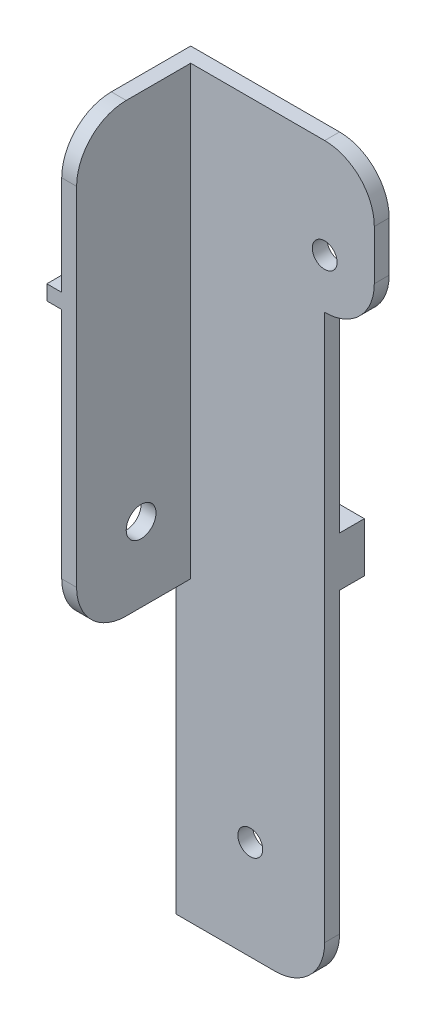
SolidWorks part; units mm, degrees
ref_plane "Front Plane" through (0, 0, 0) normal (0, 0, 1) x (1, 0, 0)
ref_plane "Top Plane" through (0, 0, 0) normal (0, 1, 0) x (1, 0, 0)
ref_plane "Right Plane" through (0, 0, 0) normal (1, 0, 0) x (0, 0, -1)
sketch "Sketch1" plane through (0, 0, 0) normal (0, 0, 1) x (1, 0, 0)
  line L0 (15, 0) -> (15, 150) construction
  line L1 (0, 0) -> (30, 0)
  line L2 (0, 0) -> (0, 150)
  line L3 (0, 150) -> (30, 150)
  line L4 (30, 0) -> (30, 120)
  line L5 (30, 150) -> (40, 150)
  line L7 (30, 120) -> (40, 120)
  line L8 (40, 150) -> (40, 120)
  line L9 (15, 75) -> (30, 75) construction
  line L10 (15, 75) -> (0, 75) construction
  line L12 (30, 75) -> (0, 75)
  line L13 (30, 75) -> (30, 80)
  line L14 (30, 80) -> (0, 80)
  line L15 (0, 75) -> (0, 80)
  line L16 (0, 75) -> (30, 75)
  line L17 (0, 75) -> (0, 70)
  line L18 (0, 70) -> (30, 70)
  line L19 (30, 75) -> (30, 70)
  circle A0 centre (15, 20) radius 2.5
  circle A1 centre (30, 130) radius 2.5
  dimension "D7" = 5
  dimension "D8" = 5
  dimension "D1" = 150
  dimension "D2" = 30
  dimension "D3" = 30
  dimension "D4" = 10
  dimension "D5" = 5
  dimension "D6" = 20
  dimension "D9" = 5
extrude "Boss-Extrude1" add sketch "Sketch1" along normal blind 3 contours L14 L4 L7 L8 L5 L3 L2 A1 | L18 L2 L1 L4 A0 region at (15, 35.1416, 0) region at (17.3969, 117.3969, 0)
sketch "Sketch2" plane through (0, 0, 3) normal (0, 0, 1) x (1, 0, 0)
  line L1 (30, 70) -> (0, 70)
  line L2 (30, 70) -> (30, 80)
  line L3 (30, 80) -> (0, 80)
  line L4 (0, 70) -> (0, 80)
extrude "Boss-Extrude2" add sketch "Sketch2" against normal blind 8
sketch "Sketch3" plane through (0, 0, 3) normal (0, 0, 1) x (1, 0, 0)
  line L0 (0, 0) -> (30, 0) construction
  line L1 (0, 150) -> (3, 150)
  line L2 (0, 150) -> (0, 0)
  line L3 (0, 0) -> (3, 0)
  line L4 (3, 150) -> (3, 0)
  dimension "D1" = 3
extrude "Boss-Extrude3" add sketch "Sketch3" along normal blind 23
sketch "Sketch4" plane through (0, 0, 0) normal (-1, 0, 0) x (0, 0, 1)
  line L0 (13, 150) -> (13, 0)
  line L1 (26, 150) -> (0, 150) construction
  line L2 (26, 0) -> (0, 0) construction
  circle A0 centre (13, 75) radius 3
  dimension "D1" = 6
extrude "Cut-Extrude1" cut sketch "Sketch4" against normal blind 23 contours L0 A0 | L0 A0 region at (0, 75, 14.2732) region at (0, 75, 11.7268)
sketch "Sketch5" plane through (0, 0, 0) normal (-1, 0, 0) x (0, 0, 1)
  line L0 (26, 150) -> (26, 0) construction
  line L1 (0, 150) -> (26, 150)
  line L2 (0, 150) -> (0, 120)
  line L3 (0, 120) -> (26, 120)
  line L4 (26, 150) -> (26, 120)
  line L6 (0, 120) -> (26, 120)
  line L7 (0, 120) -> (0, 117)
  line L8 (0, 117) -> (26, 117)
  line L9 (26, 120) -> (26, 117)
  line M5 (0, 150) -> (0, 80)
  line M11 (26, 0) -> (26, 150)
  dimension "D1" = 30
  dimension "D2" = 3
extrude "Boss-Extrude4" add sketch "Sketch5" along normal blind 3 contours L8 L3 M5 M11 region at (0, 118.5, 13)
fillet "Fillet1" radius 10 5 edges at (1.5, 0, 26) (30, 0, 1.5) (1.5, 150, 26) (40, 150, 1.5) (40, 120, 1.5)
sketch "Sketch6" plane through (0, 0, 0) normal (-1, 0, 0) x (0, 0, 1)
  line L0 (0, 70) -> (3, 70)
  line L1 (3, 70) -> (3, 0)
  line L2 (3, 0) -> (0, 0)
  line L4 (3, 0) -> (65.4541, 0)
  line L5 (3, 0) -> (3, 60)
  line L6 (3, 60) -> (65.4541, 60)
  line L7 (65.4541, 0) -> (65.4541, 60)
  line M3 (0, 0) -> (16, 0)
  arc M4 (16, 0) -> (26, 10) centre (16, 10) ccw
  line M5 (26, 10) -> (26, 117)
  dimension "D1" = 3
  dimension "D2" = 3
  dimension "D3" = 60
extrude "Cut-Extrude2" cut sketch "Sketch6" against normal blind 3 contours L4 L7 L6 M5 M4 | L6 L1 M3 M4 M5 region at (0, 30.4386, 14.3536) region at (0, 29.7505, 45.5298)
fillet "Fillet2" radius 10 1 edges at (1.5, 60, 26)
